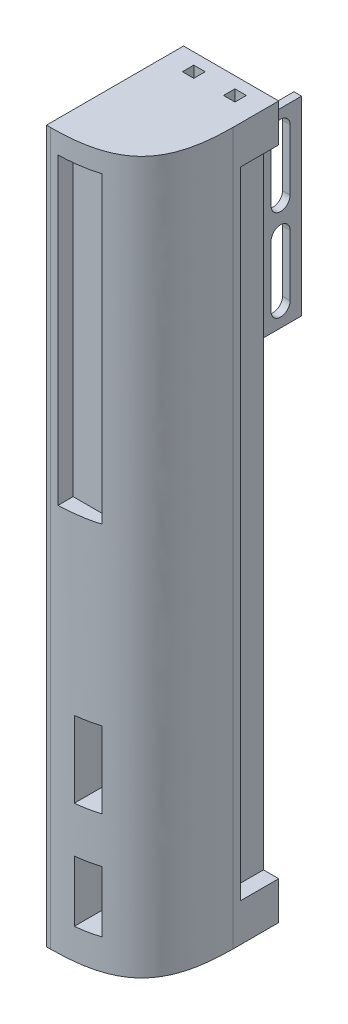
SolidWorks part; units mm, degrees
ref_plane "Front Plane" through (0, 0, 0) normal (0, 0, 1) x (1, 0, 0)
ref_plane "Top Plane" through (0, 0, 0) normal (0, 1, 0) x (1, 0, 0)
ref_plane "Right Plane" through (0, 0, 0) normal (1, 0, 0) x (0, 0, -1)
sketch "Sketch1" plane through (0, 0, 0) normal (0, 1, 0) x (1, 0, 0)
  line L1 (0, 0) -> (25, 0)
  line L2 (0, 0) -> (0, 36)
  line L3 (0, 36) -> (25, 36)
  line L4 (25, 0) -> (25, 36)
  dimension "D1" = 36
  dimension "D2" = 25
extrude "Boss-Extrude1" add sketch "Sketch1" along normal blind 186.9
fillet "Fillet1" radius 24 1 edges at (25, 93.45, 0) conic rho 0.55
sketch "Sketch2" plane through (0, 0, 0) normal (-1, 0, 0) x (0, 0, 1)
  line L0 (-24, 0) -> (0, 0) construction
  line L1 (-6.2, 83.2) -> (-1.2, 83.2)
  line L2 (-6.2, 83.2) -> (-6.2, 73.2)
  line L3 (-6.2, 73.2) -> (-1.2, 73.2)
  line L4 (-1.2, 83.2) -> (-1.2, 73.2)
  line L5 (0, 186.9) -> (0, 0) construction
  dimension "D1" = 73.2
  dimension "D2" = 1.2
  dimension "D3" = 5
  dimension "D4" = 10
extrude "Cut-Extrude1" cut sketch "Sketch2" against normal blind 4
sketch "Sketch3" plane through (0, 0, 0) normal (-1, 0, 0) x (0, 0, 1)
  line L1 (-14, 33.2) -> (-6, 33.2)
  line L2 (-14, 33.2) -> (-14, 28)
  line L3 (-14, 28) -> (-6, 28)
  line L4 (-6, 33.2) -> (-6, 28)
  line L5 (-36, 0) -> (0, 0) construction
  line L6 (0, 186.9) -> (0, 0) construction
  line L8 (-22, 33.2) -> (-30, 33.2)
  line L9 (-22, 33.2) -> (-22, 28)
  line L10 (-22, 28) -> (-30, 28)
  line L11 (-30, 33.2) -> (-30, 28)
  line L12 (-6, 61.2) -> (-14, 61.2)
  line L13 (-6, 61.2) -> (-6, 66.8)
  line L14 (-6, 66.8) -> (-14, 66.8)
  line L15 (-14, 61.2) -> (-14, 66.8)
  line L16 (-22, 66.8) -> (-30, 66.8)
  line L17 (-22, 66.8) -> (-22, 61.2)
  line L18 (-22, 61.2) -> (-30, 61.2)
  line L19 (-30, 66.8) -> (-30, 61.2)
  dimension "D1" = 28
  dimension "D2" = 6
  dimension "D3" = 8
  dimension "D4" = 5.2
  dimension "D5" = 8
  dimension "D6" = 8
  dimension "D7" = 28
  dimension "D8" = 5.6
  dimension "D9" = 8
  dimension "D10" = 6
  dimension "D11" = 8
  dimension "D12" = 5.6
  dimension "D13" = 8
extrude "Cut-Extrude2" cut sketch "Sketch3" against normal blind 10
sketch "Sketch4" plane through (0, 0, 0) normal (-1, 0, 0) x (0, 0, 1)
  line L0 (-36, 0) -> (0, 0) construction
  line L1 (-26, 160) -> (-67, 160)
  line L2 (-26, 160) -> (-26, 110)
  line L3 (-26, 110) -> (-67, 110)
  line L4 (-67, 160) -> (-67, 110)
  line L5 (-36, 186.9) -> (-36, 0) construction
  dimension "D1" = 160
  dimension "D2" = 10
  dimension "D3" = 31
  dimension "D4" = 110
extrude "Boss-Extrude2" add sketch "Sketch4" along normal blind 2
sketch "Sketch5" plane through (-2, 0, 0) normal (-1, 0, 0) x (0, 0, 1)
  line L0 (-67, 110) -> (-26, 110) construction
  line L1 (-67, 160) -> (-67, 110) construction
  line L4 (-59, 131) -> (-59, 115)
  line L6 (-64, 131) -> (-64, 115)
  line L7 (-26, 160) -> (-67, 160) construction
  line L9 (-64, 139) -> (-64, 155)
  line L11 (-59, 139) -> (-59, 155)
  arc A0 (-64, 115) -> (-59, 115) centre (-61.5, 115) ccw
  arc A2 (-59, 131) -> (-64, 131) centre (-61.5, 131) ccw
  arc A3 (-59, 155) -> (-64, 155) centre (-61.5, 155) ccw
  arc A4 (-64, 139) -> (-59, 139) centre (-61.5, 139) ccw
  dimension "D1" = 5
  dimension "D4" = 16
  dimension "D5" = 16
  dimension "D2" = 5
  dimension "D3" = 5.5
  dimension "D6" = 5
extrude "Cut-Extrude3" cut sketch "Sketch5" against normal up to next
chamfer "Chamfer1" distance 16 angle 45 1 edges at (0, 135, -36)
sketch "Sketch6" plane through (0, 0, -36) normal (0, 0, -1) x (-1, 0, 0)
  line L0 (-25, 186.9) -> (-25, 0) construction
  line L1 (-21, 182.9) -> (-15, 182.9)
  line L2 (-21, 182.9) -> (-21, 178.9)
  line L3 (-21, 178.9) -> (-15, 178.9)
  line L4 (-15, 182.9) -> (-15, 178.9)
  line L5 (-25, 186.9) -> (0, 186.9) construction
  line L6 (-1, 186.9) -> (-25, 186.9) construction
  line L7 (-10.2, 182.9) -> (-4.2, 182.9)
  line L8 (-10.2, 182.9) -> (-10.2, 178.9)
  line L9 (-10.2, 178.9) -> (-4.2, 178.9)
  line L10 (-4.2, 182.9) -> (-4.2, 178.9)
  dimension "D1" = 4
  dimension "D2" = 4
  dimension "D3" = 4
  dimension "D4" = 6
  dimension "D5" = 6
  dimension "D6" = 4.8
  dimension "D7" = 4
extrude "Cut-Extrude4" cut sketch "Sketch6" against normal blind 9
sketch "Sketch7" plane through (0, 186.9, 0) normal (0, 1, 0) x (1, 0, 0)
  line L0 (25, 24) -> (25, 36) construction
  line L1 (19.5, 33) -> (16.5, 33)
  line L2 (19.5, 33) -> (19.5, 30)
  line L3 (19.5, 30) -> (16.5, 30)
  line L4 (16.5, 33) -> (16.5, 30)
  line L5 (25, 36) -> (0, 36) construction
  line L7 (8.7, 33) -> (5.7, 33)
  line L8 (8.7, 33) -> (8.7, 30)
  line L9 (8.7, 30) -> (5.7, 30)
  line L10 (5.7, 33) -> (5.7, 30)
  dimension "D1" = 5.5
  dimension "D2" = 3
  dimension "D3" = 3
  dimension "D4" = 3
  dimension "D5" = 3
  dimension "D6" = 3
  dimension "D7" = 3
  dimension "D8" = 7.8
extrude "Cut-Extrude5" cut sketch "Sketch7" against normal blind 10
sketch "Sketch8" plane through (0, 0, 0) normal (0, -1, 0) x (1, 0, 0)
  line L0 (25, -36) -> (0, -36) construction
  line L1 (3, -5) -> (7, -5)
  line L2 (3, -5) -> (3, -33)
  line L3 (3, -33) -> (7, -33)
  line L4 (7, -5) -> (7, -29)
  line L5 (0, -36) -> (0, 0) construction
  line L6 (25, -24) -> (25, -36) construction
  line L7 (7, -33) -> (21, -33)
  line L9 (7, -29) -> (21, -29)
  line L10 (21, -33) -> (21, -29)
  dimension "D1" = 5
  dimension "D2" = 3
  dimension "D3" = 3
  dimension "D4" = 4
  dimension "D5" = 4
  dimension "D6" = 4
  dimension "D7" = 14
  dimension "D8" = 28
extrude "Boss-Extrude3" add sketch "Sketch8" along normal blind 4
sketch "Sketch9" plane through (0, 0, 0) normal (0, -1, 0) x (1, 0, 0)
  line L0 (21, -29) -> (7, -29) construction
  line L1 (7, -29) -> (7, -5) construction
  circle A0 centre (14, -22) radius 2
  dimension "D1" = 4
  dimension "D2" = 7
  dimension "D3" = 7
extrude "Cut-Extrude6" cut sketch "Sketch9" against normal blind 5
sketch "Sketch10" plane through (0, 0, 0) normal (0, -1, 0) x (1, 0, 0)
  line L0 (7, -29) -> (7, -5) construction
  circle A0 centre (14, -12) radius 1.5
  circle A1 centre (14, -22) radius 2 construction
  dimension "D1" = 7
  dimension "D2" = 10
  dimension "D3" = 3
extrude "Cut-Extrude7" cut sketch "Sketch10" against normal blind 4
sketch "Sketch11" plane through (0, 0, 0) normal (0, 0, 1) x (1, 0, 0)
  line L0 (0, 186.9) -> (0, 0) construction
  line L1 (7, 24) -> (13, 24)
  line L2 (7, 24) -> (7, 8)
  line L3 (7, 8) -> (13, 8)
  line L4 (13, 24) -> (13, 8)
  line L5 (0, 0) -> (1, 0) construction
  line L7 (7, 36) -> (13, 36)
  line L8 (7, 36) -> (7, 56)
  line L9 (7, 56) -> (13, 56)
  line L10 (13, 36) -> (13, 56)
  dimension "D1" = 7
  dimension "D2" = 8
  dimension "D3" = 16
  dimension "D4" = 6
  dimension "D5" = 12
  dimension "D6" = 6
  dimension "D7" = 20
  dimension "D8" = 7
extrude "Cut-Extrude8" cut sketch "Sketch11" against normal blind 8
sketch "Sketch12" plane through (0, 0, 0) normal (0, 0, 1) x (1, 0, 0)
  line L0 (0, 186.9) -> (0, 0) construction
  line L1 (3, 181.6) -> (13, 181.6)
  line L2 (3, 181.6) -> (3, 101.9)
  line L3 (3, 101.9) -> (13, 101.9)
  line L4 (13, 181.6) -> (13, 101.9)
  line L5 (25, 186.9) -> (1, 186.9) construction
  dimension "D1" = 3
  dimension "D2" = 5.3
  dimension "D3" = 10
  dimension "D4" = 79.7
extrude "Cut-Extrude9" cut sketch "Sketch12" against normal blind 4
sketch "Sketch13" plane through (25, 0, 0) normal (1, 0, 0) x (0, 0, -1)
  line L0 (36, 186.9) -> (36, 0) construction
  line L1 (36, 176.9) -> (26, 176.9)
  line L2 (36, 176.9) -> (36, 10)
  line L3 (36, 10) -> (26, 10)
  line L4 (26, 176.9) -> (26, 10)
  line L5 (24, 186.9) -> (36, 186.9) construction
  line L6 (24, 0) -> (36, 0) construction
  dimension "D1" = 10
  dimension "D2" = 10
  dimension "D3" = 10
extrude "Cut-Extrude10" cut sketch "Sketch13" against normal blind 4
